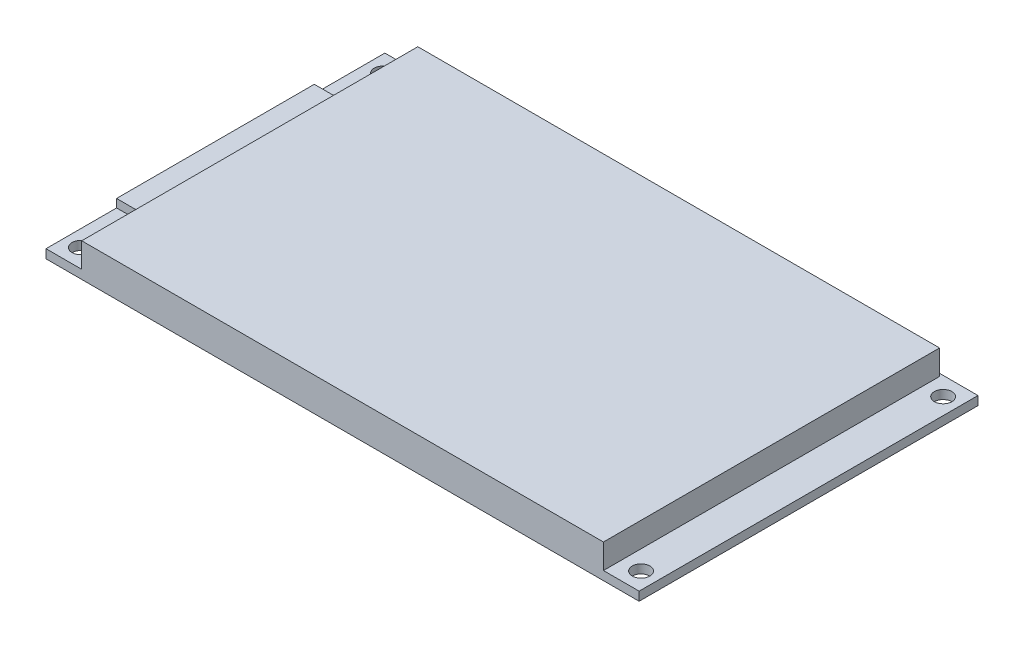
SolidWorks part; units mm, degrees
other "标注1"
sketch "草图6" plane through (-54, 6.1, 30.85) normal (-0.2175, 0.9751, 0.0424) x (0.9753, 0.2154, 0.05)
ref_plane "前视基准面" through (0, 0, 0) normal (0, 0, 1) x (1, 0, 0)
ref_plane "上视基准面" through (0, 0, 0) normal (0, 1, 0) x (1, 0, 0)
ref_plane "右视基准面" through (0, 0, 0) normal (1, 0, 0) x (0, 0, -1)
sketch "草图1" plane through (0, 0, 0) normal (0, 1, 0) x (1, 0, 0)
  line L1 (-54, 30.85) -> (54, 30.85)
  line L2 (-54, 30.85) -> (-54, -30.85)
  line L3 (-54, -30.85) -> (54, -30.85)
  line L4 (54, 30.85) -> (54, -30.85)
  line L5 (-54, 30.85) -> (54, -30.85) construction
  line L6 (-54, -30.85) -> (54, 30.85) construction
  point P0 (0, 0)
  dimension "D1" = 108
  dimension "D2" = 61.7
extrude "PCB" add sketch "草图1" along normal blind 1.6
sketch "草图2" plane through (0, 1.6, 0) normal (0, 1, 0) x (1, 0, 0)
  line L0 (-54, 30.85) -> (-54, -30.85) construction
  line L1 (-47.5, 30.35) -> (47.5, 30.35)
  line L2 (-47.5, 30.35) -> (-47.5, -30.85)
  line L3 (-47.5, -30.85) -> (47.5, -30.85)
  line L4 (47.5, 30.35) -> (47.5, -30.85)
  line L5 (54, -30.85) -> (54, 30.85) construction
  line L6 (54, 30.85) -> (-54, 30.85) construction
  line L7 (-54, -30.85) -> (54, -30.85) construction
  dimension "D1" = 6.5
  dimension "D2" = 6.5
  dimension "D3" = 0.5
extrude "面板" add sketch "草图2" along normal blind 4.5
sketch "草图4" plane through (0, 1.6, 0) normal (0, 1, 0) x (1, 0, 0)
  line L0 (-3.355, 0) -> (3.355, 0) construction
  line L1 (-50.5, 18) -> (-54, 18)
  line L2 (-50.5, 18) -> (-50.5, -18)
  line L3 (-50.5, -18) -> (-54, -18)
  line L4 (-54, 18) -> (-54, -18)
  line L5 (-50.5, 18) -> (-54, -18) construction
  line L6 (-50.5, -18) -> (-54, 18) construction
  line L7 (-54, 30.85) -> (-54, -30.85) construction
  point P0 (-52.25, 0)
  dimension "D1" = 3.5
  dimension "D2" = 36
extrude "凸台-拉伸3" add sketch "草图4" along normal blind 1.5
extrude "凸台-拉伸4" add sketch "草图4<2>" against normal blind 8.5 from surface starting at face at (0, 0, 0)
sketch "草图4<2>" plane through (0, 1.6, 0) normal (0, 1, 0) x (1, 0, 0) same geometry as "草图4"
sketch "螺丝孔定位" plane through (0, 0, 0) normal (0, -1, 0) x (-1, 0, 0)
  line L1 (-51, 27.5) -> (51, 27.5) construction
  line L2 (-51, 27.5) -> (-51, -27.5) construction
  line L3 (-51, -27.5) -> (51, -27.5) construction
  line L4 (51, 27.5) -> (51, -27.5) construction
  line L5 (-51, 27.5) -> (51, -27.5) construction
  line L6 (-51, -27.5) -> (51, 27.5) construction
  point P0 (0, 0)
  dimension "D1" = 102
  dimension "D2" = 55
hole_wizard "M3 间隙孔1" positions "草图7" profile "草图8" hole size "M3" standard "ISO" end condition up to next
sketch "草图7" plane through (0, 1.6, 0) normal (0, 1, 0) x (1, 0, 0)
  point P0 (-51, 27.5)
  point P2 (-51, -27.5)
  point P4 (51, 27.5)
  point P6 (51, -27.5)
sketch "草图8" plane through (-51, 1.6, -27.5) normal (1, 0, 0) x (0, 0, 1)
  line L0 (0, 0) -> (0, 1.6)
  line L1 (0, 1.6) -> (1.6, 1.6)
  line L2 (1.6, 1.6) -> (1.6, 0)
  line L5 (1.6, 0) -> (0, 0)
  line L11 (0, -6.35) -> (0, 107.95) construction
  dimension "通孔孔直径" = 3.2
  dimension "通孔孔深度" = 1.6
